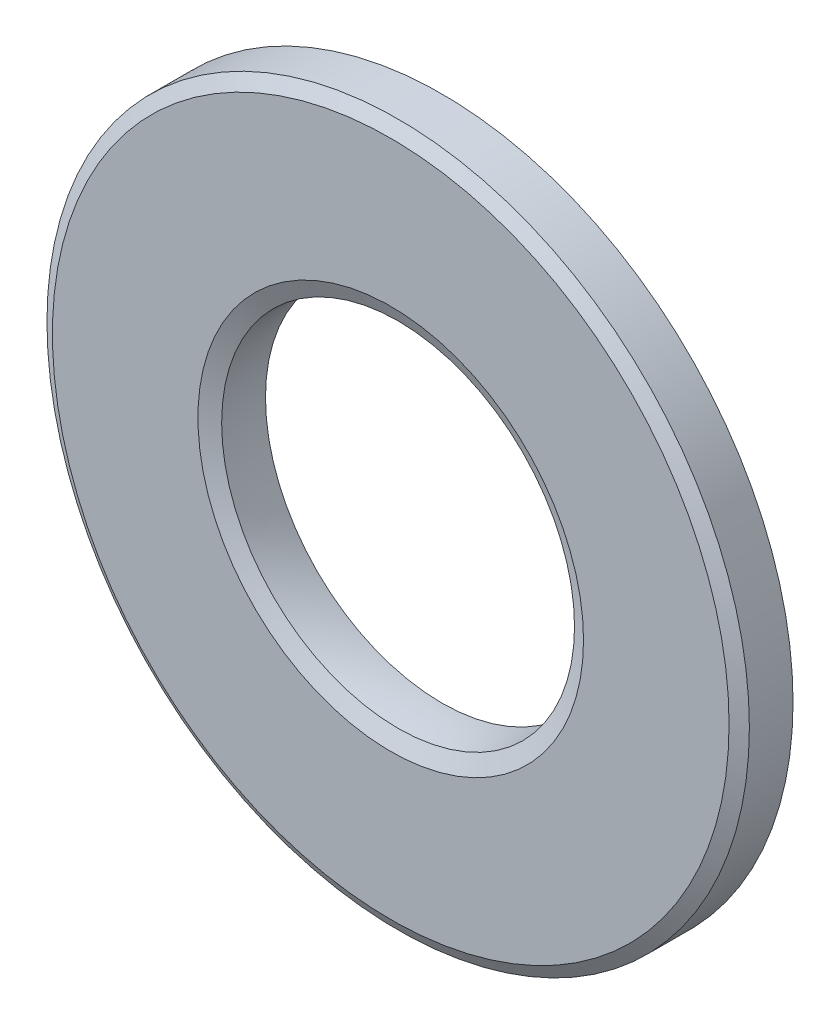
SolidWorks part; units mm, degrees
other "Imported1" parameters "D1"=0.254
ref_plane "Front Plane" through (0, 0, 0) normal (0, 0, 1) x (1, 0, 0)
ref_plane "Top Plane" through (0, 0, 0) normal (0, 1, 0) x (1, 0, 0)
ref_plane "Right Plane" through (0, 0, 0) normal (1, 0, 0) x (0, 0, -1)
sketch "Sketch1" plane through (0, 0, 0) normal (0, 0, 1) x (1, 0, 0)
  line L0 (-12, 0) -> (12, 0) construction
  line L1 (-6, 0) -> (6, 0) construction
  circle A0 centre (0, 0) radius 6 construction
  circle A1 centre (0, 0) radius 12 construction
  point P8 (0, 0)
  point P9 (0, 12)
  point P11 (6, 0)
  dimension "ID" = 12
  dimension "OD" = 24
sketch "Sketch2" plane through (0, 0, 0) normal (1, 0, 0) x (0, 0, -1)
  line L0 (-1, 12) -> (1, 12) construction
  point P2 (0, 12)
  dimension "Thickness" = 2
sketch "Sketch3" plane through (0, 0, 0) normal (0, 0, 1) x (1, 0, 0)
  circle A0 centre (0, 0) radius 6
  circle A1 centre (0, 0) radius 12
extrude "Boss-Extrude1" add sketch "Sketch3" along normal up to vertex (1 mm away) and the other way up to vertex (1 mm away) up to point (0, 12, 1) other way up to point (0, 12, -1)
chamfer "Chamfer1" distance 0.254 angle 60 2 edges at (12, 0, -1) (12, 0, 1)
sketch "Sketch4" plane through (0, 0, 0) normal (1, 0, 0) x (0, 0, -1)
  line L3 (-1, 5.9492) -> (-1, 6.0508)
  line L4 (-1, 5.9492) -> (1, 5.9492)
  line L5 (1, 5.9492) -> (1, 6.0508)
  line L6 (-1, 0) -> (1, 0) construction
  arc A0 (-1, 6.0508) -> (1, 6.0508) centre (0, 15.8679) ccw
  point P0 (0, 6)
  point P9 (-1, 6)
  point P13 (0, 0)
  dimension "D1" = 0.0508
revolve "Cut-Revolve1" cut sketch "Sketch4" angle 360 about L6
chamfer "Chamfer2" distance 0.254 angle 60 2 edges at (0, -6.0508, -1) (0, -6.0508, 1)
equation "\"D1@Chamfer2\"=\"D1@Chamfer1\""
